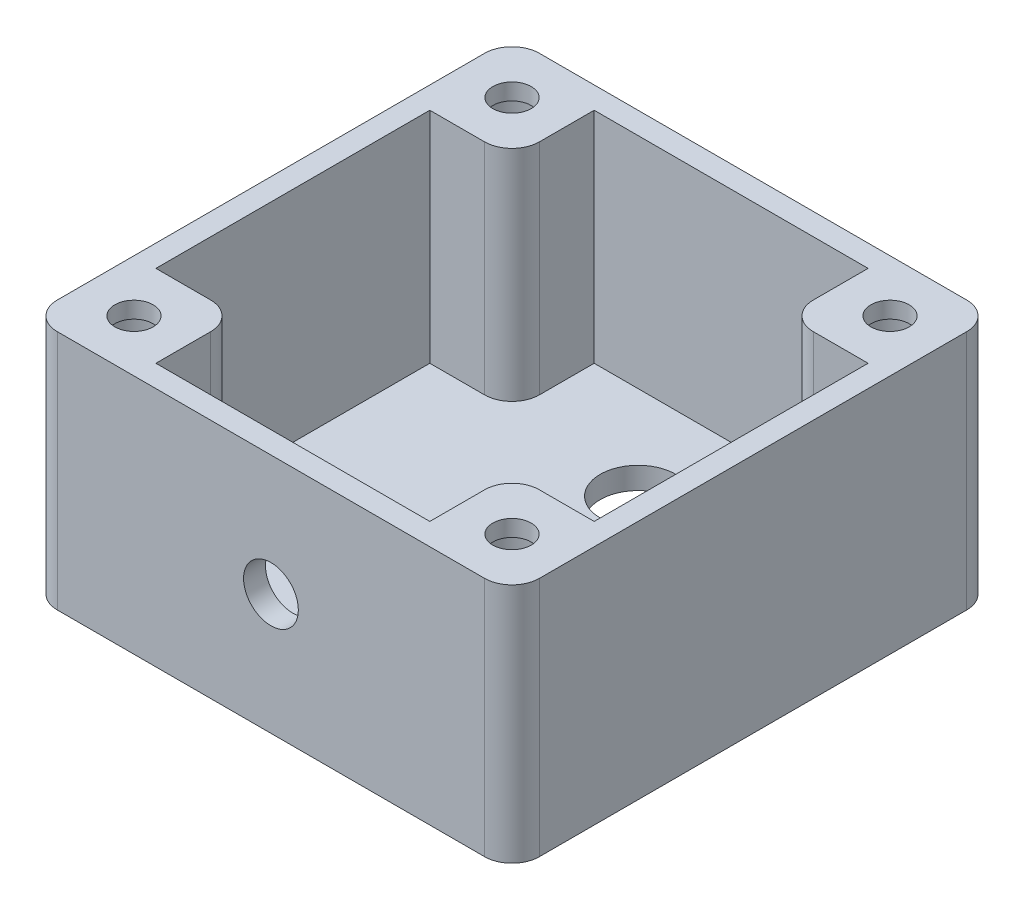
SolidWorks part; units mm, degrees
ref_plane "Front" through (0, 0, 0) normal (0, 0, 1) x (1, 0, 0)
ref_plane "Top" through (0, 0, 0) normal (0, 1, 0) x (1, 0, 0)
ref_plane "Right" through (0, 0, 0) normal (1, 0, 0) x (0, 0, -1)
sketch "Sketch1" plane through (0, 0, 0) normal (0, 1, 0) x (1, 0, 0)
  line L1 (-12.5, -20) -> (12.5, -20)
  line L2 (-12.5, -20) -> (-12.5, 20)
  line L3 (-12.5, 20) -> (12.5, 20)
  line L4 (12.5, -20) -> (12.5, 20)
  line L5 (-12.5, -20) -> (12.5, 20) construction
  line L6 (-12.5, 20) -> (12.5, -20) construction
  line L7 (-22, -22) -> (22, -22)
  line L8 (-22, -22) -> (-22, 22)
  line L9 (-22, 22) -> (22, 22)
  line L10 (22, -22) -> (22, 22)
  line L11 (-22, -22) -> (22, 22) construction
  line L12 (-22, 22) -> (22, -22) construction
  point P0 (0, 0)
  point P10 (0, 0)
  dimension "D5" = 40
  dimension "D6" = 25
  dimension "D7" = 9.5
  dimension "D8" = 2
extrude "Boss-Extrude4" add sketch "Sketch1" along normal blind 20
sketch "Sketch4" plane through (0, 0, 0) normal (0, -1, 0) x (1, 0, 0)
  line L1 (22, -22) -> (-22, -22)
  line L2 (22, -22) -> (22, 22)
  line L3 (22, 22) -> (-22, 22)
  line L4 (-22, -22) -> (-22, 22)
  line L5 (22, -22) -> (-22, 22) construction
  line L6 (22, 22) -> (-22, -22) construction
  point P0 (0, 0)
extrude "Boss-Extrude5" add sketch "Sketch4" along normal blind 2
sketch "Sketch5" plane through (0, 0, 0) normal (0, 1, 0) x (1, 0, 0)
  line L0 (9.25, 12.799) -> (9.25, 10.201)
  line L1 (12.5, 20) -> (-12.5, 20) construction
  circle A0 centre (0, 11.5) radius 3.45
  arc A1 (9.25, 12.799) -> (9.25, 10.201) centre (8.5, 11.5) ccw
  dimension "D1" = 6.9
  dimension "D3" = 3
  dimension "D2" = 8.5
  dimension "D4" = 8.5
  dimension "D5" = 0.75
extrude "Cut-Extrude2" cut sketch "Sketch5" against normal blind 2
sketch "Sketch6" plane through (0, 20, 0) normal (0, 1, 0) x (1, 0, 0)
  line L0 (0, 22) -> (0, -22) construction
  line L1 (22, 22) -> (-22, 22) construction
  line L2 (-22, -22) -> (22, -22) construction
  line L3 (-12.5, -20) -> (-22, -20) construction
  line L4 (-22, 22) -> (-22, -22) construction
  line L5 (-17.25, -20) -> (-17.25, 22) construction
  circle A0 centre (-17.25, 17.25) radius 1.75
  circle A1 centre (-17.25, -17.25) radius 1.75
  dimension "D2" = 3.5
  dimension "D1" = 4.75
  dimension "D3" = 4.75
  dimension "D4" = 4.75
extrude "Cut-Extrude3" cut sketch "Sketch6" against normal through all
mirror "Mirror1" about plane through (0, 0, 0) normal (1, 0, 0) of "Cut-Extrude3"
sketch "Sketch7" plane through (0, -2, 0) normal (0, -1, 0) x (1, 0, 0)
  circle A0 centre (-17.25, 17.25) radius 3.25
  circle A1 centre (17.25, 17.25) radius 3.25
  circle A2 centre (17.25, -17.25) radius 3.25
  circle A3 centre (-17.25, -17.25) radius 3.25
  point P11 (-18.5, -18.5)
  point P13 (-17.25, -18.5)
  dimension "D1" = 6.5
extrude "Cut-Extrude4" cut sketch "Sketch7" against normal offset from surface (20.5 mm away) 1.5 up to face at (17.25, 20, -15.5)
sketch "Sketch10" plane through (0, 20, 0) normal (0, 1, 0) x (1, 0, 0)
  line L0 (-12.5, 20) -> (-12.5, -20) construction
  line L1 (-12.5, 12.5) -> (-20, 12.5)
  line L2 (-12.5, 12.5) -> (-12.5, -12.5)
  line L3 (-12.5, -12.5) -> (-20, -12.5)
  line L4 (-20, 12.5) -> (-20, -12.5)
  line L5 (-22, 22) -> (-22, -22) construction
  line L7 (-22, 22) -> (22, 22) construction
  line L8 (12.5, 20) -> (-12.5, 20) construction
  circle A0 centre (-17.25, 17.25) radius 1.75 construction
  circle A1 centre (-17.25, -17.25) radius 1.75 construction
  dimension "D3" = 4.75
  dimension "D1" = 2
  dimension "D2" = 2
  dimension "D4" = 4.75
  dimension "D5" = 4.75
extrude "Cut-Extrude5" cut sketch "Sketch10" against normal up to surface (20 mm away) up to face at (0, 0, -8.05)
mirror "Mirror2" about plane through (0, 0, 0) normal (1, 0, 0) of "Cut-Extrude5"
sketch "Sketch11" plane through (0, 0, 22) normal (0, 0, 1) x (1, 0, 0)
  line L0 (-22, 9) -> (22, 9) construction
  line L1 (-22, 20) -> (-22, -2) construction
  line L2 (22, 20) -> (22, -2) construction
  circle A0 centre (0, 9) radius 2.5
  dimension "D1" = 5
extrude "Cut-Extrude6" cut sketch "Sketch11" against normal up to next
fillet "Fillet1" radius 2.5 8 edges at (-22, 9, 22) (22, 9, 22) (22, 9, -22) (12.5, 10, 12.5) (-12.5, 10, 12.5) (12.5, 10, -12.5) (-12.5, 10, -12.5) (-22, 9, -22)
equation "\"D1@Sketch6\"=\"D3@Sketch6\""
equation "\"D4@Sketch6\"=\"D3@Sketch6\""
equation "\"D1@Sketch10\"=\"D2@Sketch10\""
equation "\"D4@Sketch10\"=\"D3@Sketch10\""
equation "\"D5@Sketch10\"=\"D4@Sketch10\""
equation "\"D7@Sketch1\"=(\"D5@Sketch1\"+2*\"D8@Sketch1\"-\"D6@Sketch1\")/2"
equation "\"D5@Sketch5\"=\"D3@Sketch5\"/4"
